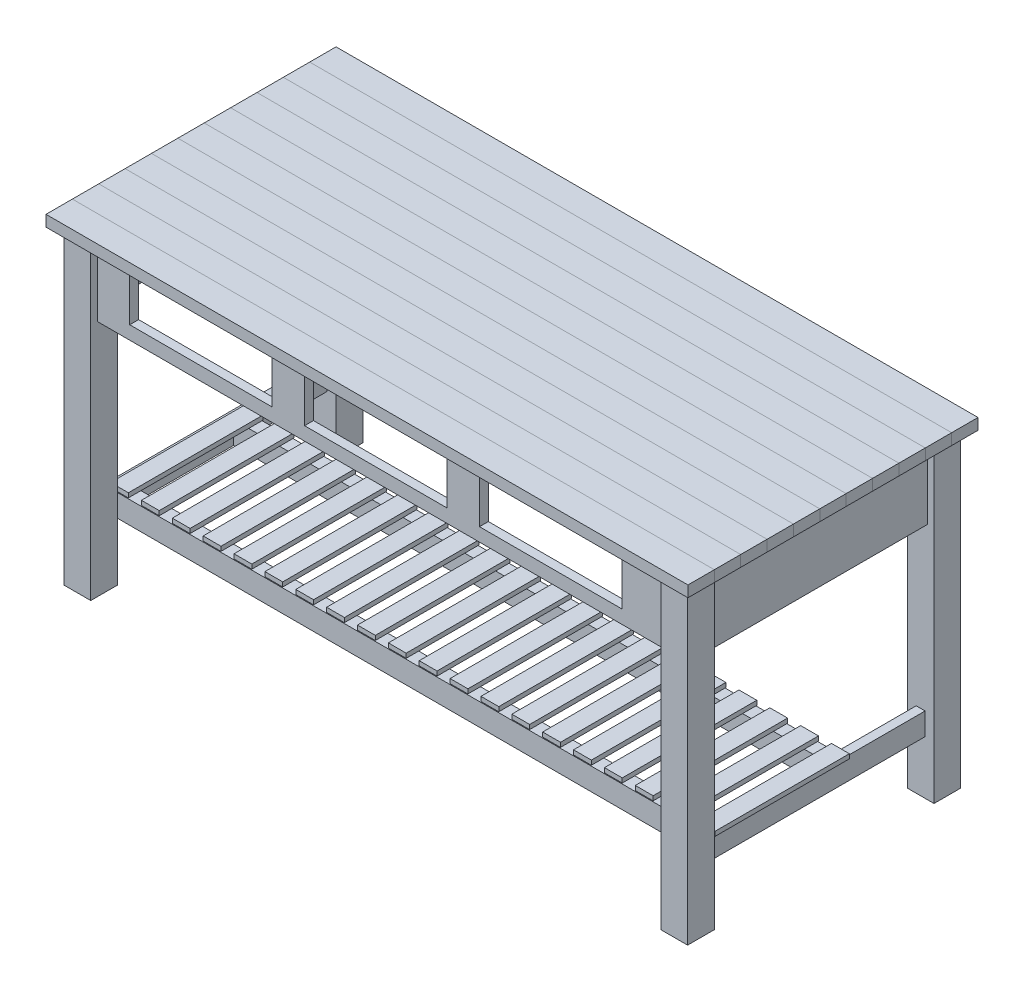
SolidWorks part; units mm, degrees
ref_plane "Default Plane" through (914.4, 31.75, 137.455) normal (0, -1, 0) x (-1, 0, 0)
sketch3d "Bounding-Box_Cut-List-Item1"
  line L0 (0, 75.184, 0) -> (1830.3875, 75.184, 0) construction
  line L1 (1830.3875, 75.184, 0) -> (1830.3875, 0, 0) construction
  line L2 (1830.3875, 0, 0) -> (0, 0, 0) construction
  line L3 (0, 0, 0) -> (0, 75.184, 0) construction
  line L4 (0, 75.184, 31.75) -> (1830.3875, 75.184, 31.75) construction
  line L5 (1830.3875, 75.184, 31.75) -> (1830.3875, 0, 31.75) construction
  line L6 (1830.3875, 0, 31.75) -> (0, 0, 31.75) construction
  line L7 (0, 0, 31.75) -> (0, 75.184, 31.75) construction
  line L8 (0, 75.184, 0) -> (0, 75.184, 31.75) construction
  line L9 (1830.3875, 75.184, 0) -> (1830.3875, 75.184, 31.75) construction
  line L10 (1830.3875, 0, 0) -> (1830.3875, 0, 31.75) construction
  line L11 (0, 0, 0) -> (0, 0, 31.75) construction
ref_plane "Default Plane" through (890.5875, 0, -664.169) normal (-1, 0, 0) x (0, 0, 1)
sketch3d "Bounding-Box_Cut-List-Item4"
  line L0 (76.2, 0, 0) -> (76.2, -882.65, 0) construction
  line L1 (76.2, -882.65, 0) -> (0, -882.65, 0) construction
  line L2 (0, -882.65, 0) -> (0, 0, 0) construction
  line L3 (0, 0, 0) -> (76.2, 0, 0) construction
  line L4 (76.2, 0, 76.2) -> (76.2, -882.65, 76.2) construction
  line L5 (76.2, -882.65, 76.2) -> (0, -882.65, 76.2) construction
  line L6 (0, -882.65, 76.2) -> (0, 0, 76.2) construction
  line L7 (0, 0, 76.2) -> (76.2, 0, 76.2) construction
  line L8 (76.2, 0, 0) -> (76.2, 0, 76.2) construction
  line L9 (76.2, -882.65, 0) -> (76.2, -882.65, 76.2) construction
  line L10 (0, -882.65, 0) -> (0, -882.65, 76.2) construction
  line L11 (0, 0, 0) -> (0, 0, 76.2) construction
ref_plane "Default Plane" through (865.1875, -666.75, -587.969) normal (-1, 0, 0) x (0, 0, 1)
sketch3d "Bounding-Box_Cut-List-Item5"
  line L0 (0, -63.5, 0) -> (624.84, -63.5, 0) construction
  line L1 (624.84, -63.5, 0) -> (624.84, 0, 0) construction
  line L2 (624.84, 0, 0) -> (0, 0, 0) construction
  line L3 (0, 0, 0) -> (0, -63.5, 0) construction
  line L4 (0, -63.5, 25.4) -> (624.84, -63.5, 25.4) construction
  line L5 (624.84, -63.5, 25.4) -> (624.84, 0, 25.4) construction
  line L6 (624.84, 0, 25.4) -> (0, 0, 25.4) construction
  line L7 (0, 0, 25.4) -> (0, -63.5, 25.4) construction
  line L8 (0, -63.5, 0) -> (0, -63.5, 25.4) construction
  line L9 (624.84, -63.5, 0) -> (624.84, -63.5, 25.4) construction
  line L10 (624.84, 0, 0) -> (624.84, 0, 25.4) construction
  line L11 (0, 0, 0) -> (0, 0, 25.4) construction
ref_plane "Default Plane" through (-812.8, 0, 36.871) normal (-1, 0, 0) x (0, 0, 1)
sketch3d "Bounding-Box_Cut-List-Item6"
  line L0 (76.2, 0, 0) -> (76.2, -882.65, 0) construction
  line L1 (76.2, -882.65, 0) -> (-701.04, -882.65, 0) construction
  line L2 (-701.04, -882.65, 0) -> (-701.04, 0, 0) construction
  line L3 (-701.04, 0, 0) -> (76.2, 0, 0) construction
  line L4 (76.2, 0, 77.7875) -> (76.2, -882.65, 77.7875) construction
  line L5 (76.2, -882.65, 77.7875) -> (-701.04, -882.65, 77.7875) construction
  line L6 (-701.04, -882.65, 77.7875) -> (-701.04, 0, 77.7875) construction
  line L7 (-701.04, 0, 77.7875) -> (76.2, 0, 77.7875) construction
  line L8 (76.2, 0, 0) -> (76.2, 0, 77.7875) construction
  line L9 (76.2, -882.65, 0) -> (76.2, -882.65, 77.7875) construction
  line L10 (-701.04, -882.65, 0) -> (-701.04, -882.65, 77.7875) construction
  line L11 (-701.04, 0, 0) -> (-701.04, 0, 77.7875) construction
material "Beech"
ref_plane "Front Plane" through (0, 0, 0) normal (0, 0, 1) x (1, 0, 0)
ref_plane "Top Plane" through (0, 0, 0) normal (0, 1, 0) x (1, 0, 0)
ref_plane "Right Plane" through (0, 0, 0) normal (1, 0, 0) x (0, 0, -1)
sketch "Sketch1" plane through (0, 0, 0) normal (0, 1, 0) x (1, 0, 0)
  line L0 (0, -450.3596) -> (0, 450.3596) construction
  line L1 (-915.9875, -62.271) -> (914.4, -62.271)
  line L2 (-915.9875, -62.271) -> (-915.9875, -137.455)
  line L3 (-915.9875, -137.455) -> (914.4, -137.455)
  line L4 (914.4, -62.271) -> (914.4, -137.455)
  line L6 (-915.9875, -62.271) -> (914.4, -62.271)
  line L7 (-915.9875, -62.271) -> (-915.9875, 12.913)
  line L8 (-915.9875, 12.913) -> (914.4, 12.913)
  line L9 (914.4, -62.271) -> (914.4, 12.913)
  line L10 (-915.9875, 12.913) -> (914.4, 12.913)
  line L11 (-915.9875, 12.913) -> (-915.9875, 88.097)
  line L12 (-915.9875, 88.097) -> (914.4, 88.097)
  line L13 (914.4, 12.913) -> (914.4, 88.097)
  line L14 (-915.9875, 88.097) -> (914.4, 88.097)
  line L15 (-915.9875, 88.097) -> (-915.9875, 163.281)
  line L16 (-915.9875, 163.281) -> (914.4, 163.281)
  line L17 (914.4, 88.097) -> (914.4, 163.281)
  line L18 (-915.9875, 163.281) -> (914.4, 163.281)
  line L19 (-915.9875, 163.281) -> (-915.9875, 238.465)
  line L20 (-915.9875, 238.465) -> (914.4, 238.465)
  line L21 (914.4, 163.281) -> (914.4, 238.465)
  line L22 (-915.9875, 238.465) -> (914.4, 238.465)
  line L23 (-915.9875, 238.465) -> (-915.9875, 313.649)
  line L24 (-915.9875, 313.649) -> (914.4, 313.649)
  line L25 (914.4, 238.465) -> (914.4, 313.649)
  line L26 (-915.9875, 313.649) -> (914.4, 313.649)
  line L27 (-915.9875, 313.649) -> (-915.9875, 388.833)
  line L28 (-915.9875, 388.833) -> (914.4, 388.833)
  line L29 (914.4, 313.649) -> (914.4, 388.833)
  line L30 (-915.9875, 388.833) -> (914.4, 388.833)
  line L31 (-915.9875, 388.833) -> (-915.9875, 464.017)
  line L32 (-915.9875, 464.017) -> (914.4, 464.017)
  line L33 (914.4, 388.833) -> (914.4, 464.017)
  line L34 (-915.9875, 464.017) -> (914.4, 464.017)
  line L35 (-915.9875, 464.017) -> (-915.9875, 539.201)
  line L36 (-915.9875, 539.201) -> (914.4, 539.201)
  line L37 (914.4, 464.017) -> (914.4, 539.201)
  line L38 (-915.9875, 539.201) -> (914.4, 539.201)
  line L39 (-915.9875, 539.201) -> (-915.9875, 614.385)
  line L40 (-915.9875, 614.385) -> (914.4, 614.385)
  line L41 (914.4, 539.201) -> (914.4, 614.385)
  line L42 (-915.9875, 614.385) -> (914.4, 614.385)
  line L44 (-915.9875, 614.385) -> (914.4, 614.385)
  line L46 (914.4, -137.455) -> (-915.9875, -137.455)
  line L47 (-915.9875, 614.385) -> (914.4, 614.385)
  line L48 (-915.9875, 614.385) -> (-915.9875, 689.569)
  line L49 (-915.9875, 689.569) -> (914.4, 689.569)
  line L50 (914.4, 614.385) -> (914.4, 689.569)
  dimension "D1" = 75.184
  dimension "D2" = 1830.3875
  dimension "D3" = 914.4
  dimension "D4" = 75.184
extrude "top1" add sketch "Sketch1" along normal blind 31.75 contours L4 L1 L2 L3 region at (-0.7938, 0, 99.863)
extrude "top2" add sketch "Sketch1<9>" along normal blind 31.75 separate body contours L1 L9 L8 L7 region at (-0.7938, 0, 24.679)
sketch "Sketch1<9>" plane through (0, 0, 0) normal (0, 1, 0) x (1, 0, 0) same geometry as "Sketch1"
extrude "top3" add sketch "Sketch1<10>" along normal blind 31.75 separate body contours L8 L13 L12 L11 region at (-0.7938, 0, -50.505)
sketch "Sketch1<10>" plane through (0, 0, 0) normal (0, 1, 0) x (1, 0, 0) same geometry as "Sketch1"
extrude "top4" add sketch "Sketch1<11>" along normal blind 31.75 separate body contours L12 L17 L16 L15 region at (-0.7938, 0, -125.689)
sketch "Sketch1<11>" plane through (0, 0, 0) normal (0, 1, 0) x (1, 0, 0) same geometry as "Sketch1"
extrude "top5" add sketch "Sketch1<12>" along normal blind 31.75 separate body contours L16 L21 L20 L19 region at (-0.7938, 0, -200.873)
sketch "Sketch1<12>" plane through (0, 0, 0) normal (0, 1, 0) x (1, 0, 0) same geometry as "Sketch1"
extrude "top6" add sketch "Sketch1<13>" along normal blind 31.75 separate body contours L20 L25 L24 L23 region at (-0.7938, 0, -276.057)
sketch "Sketch1<13>" plane through (0, 0, 0) normal (0, 1, 0) x (1, 0, 0) same geometry as "Sketch1"
extrude "top7" add sketch "Sketch1<14>" along normal blind 31.75 separate body contours L24 L29 L28 L27 region at (-0.7938, 0, -351.241)
sketch "Sketch1<14>" plane through (0, 0, 0) normal (0, 1, 0) x (1, 0, 0) same geometry as "Sketch1"
extrude "top8" add sketch "Sketch1<15>" along normal blind 31.75 separate body contours L28 L33 L32 L31 region at (-0.7938, 0, -426.425)
sketch "Sketch1<15>" plane through (0, 0, 0) normal (0, 1, 0) x (1, 0, 0) same geometry as "Sketch1"
extrude "top9" add sketch "Sketch1<16>" along normal blind 31.75 separate body contours L32 L37 L36 L35 region at (-0.7938, 0, -501.609)
sketch "Sketch1<16>" plane through (0, 0, 0) normal (0, 1, 0) x (1, 0, 0) same geometry as "Sketch1"
extrude "top10" add sketch "Sketch1<17>" along normal blind 31.75 separate body contours L36 L41 L40 L39 region at (-0.7938, 0, -576.793)
sketch "Sketch1<17>" plane through (0, 0, 0) normal (0, 1, 0) x (1, 0, 0) same geometry as "Sketch1"
extrude "top11" add sketch "Sketch1<20>" along normal blind 31.75 separate body contours L3 L49 region at (-0.7938, 0, -651.977)
sketch "Sketch1<20>" plane through (0, 0, 0) normal (0, 1, 0) x (1, 0, 0) same geometry as "Sketch1"
sketch "Sketch2" plane through (0, 0, 0) normal (0, 1, 0) x (1, 0, 0)
  line L0 (-915.9875, 614.385) -> (-915.9875, 689.569) construction
  line L1 (-889, -113.071) -> (-812.8, -113.071)
  line L2 (-889, -113.071) -> (-889, -36.871)
  line L3 (-889, -36.871) -> (-812.8, -36.871)
  line L4 (-812.8, -113.071) -> (-812.8, -36.871)
  line L5 (-890.5875, 587.969) -> (-814.3875, 587.969)
  line L6 (-890.5875, 587.969) -> (-890.5875, 664.169)
  line L7 (-890.5875, 664.169) -> (-814.3875, 664.169)
  line L8 (-814.3875, 587.969) -> (-814.3875, 664.169)
  line L10 (0, -1000) -> (0, 49000) construction
  line L11 (814.3875, 587.969) -> (814.3875, 664.169)
  line L12 (890.5875, 664.169) -> (814.3875, 664.169)
  line L13 (890.5875, 587.969) -> (890.5875, 664.169)
  line L14 (890.5875, 587.969) -> (814.3875, 587.969)
  line L15 (812.8, -113.071) -> (812.8, -36.871)
  line L16 (889, -36.871) -> (812.8, -36.871)
  line L17 (889, -113.071) -> (889, -36.871)
  line L18 (889, -113.071) -> (812.8, -113.071)
  line L20 (-915.9875, 689.569) -> (914.4, 689.569) construction
  dimension "D1" = 76.2
  dimension "D2" = 76.2
  dimension "D3" = 25.4
  dimension "D4" = 25.4
extrude "table legs" add sketch "Sketch2" against normal blind 882.65 separate body
ref_plane "Plane6" through (0, 0, -587.969) normal (0, 0, 1) x (1, 0, 0)
sketch "Sketch4" plane through (0, 0, -587.969) normal (0, 0, 1) x (1, 0, 0)
  line L0 (814.3875, -882.65) -> (890.5875, -882.65) construction
  line L1 (839.7875, -666.75) -> (865.1875, -666.75)
  line L2 (839.7875, -666.75) -> (839.7875, -730.25)
  line L3 (839.7875, -730.25) -> (865.1875, -730.25)
  line L4 (865.1875, -666.75) -> (865.1875, -730.25)
  line L5 (814.3875, -882.65) -> (814.3875, 0) construction
  line L6 (890.5875, -882.65) -> (890.5875, 0) construction
  point P4 (852.4875, -882.65)
  dimension "D1" = 152.4
  dimension "D2" = 25.4
  dimension "D3" = 63.5
  dimension "D4" = 25.4
extrude "stretcher width" add sketch "Sketch4" along normal up to surface (624.84 mm away) separate body up to face at (850.9, -441.325, 36.871)
mirror "Mirror4" about plane through (0, 0, 0) normal (1, 0, 0) of "stretcher width"
ref_plane "Plane7" through (-839.7875, 0, 0) normal (1, 0, 0) x (0, 0, -1)
sketch "Sketch5" plane through (-839.7875, 0, 0) normal (1, 0, 0) x (0, 0, -1)
  line L1 (-36.871, -666.75) -> (587.969, -666.75) construction
  line L2 (-24.171, -666.75) -> (13.929, -666.75)
  line L3 (-24.171, -666.75) -> (-24.171, -730.25)
  line L4 (-24.171, -730.25) -> (13.929, -730.25)
  line L5 (13.929, -666.75) -> (13.929, -730.25)
  line L6 (-36.871, -730.25) -> (587.969, -730.25) construction
  line L7 (-36.871, -882.65) -> (-36.871, 0) construction
  line L8 (587.969, -666.75) -> (587.969, -730.25) construction
  line L9 (359.369, -666.75) -> (321.269, -666.75)
  line L10 (359.369, -666.75) -> (359.369, -730.25)
  line L11 (359.369, -730.25) -> (321.269, -730.25)
  line L12 (321.269, -666.75) -> (321.269, -730.25)
  dimension "D1" = 12.7
  dimension "D2" = 38.1
  dimension "D3" = 228.6
  dimension "D4" = 38.1
extrude "stretcher length" add sketch "Sketch5" along normal up to surface (1679.575 mm away) separate body up to face at (839.7875, -698.5, -275.549)
ref_plane "Plane9" through (-812.8, 0, 0) normal (1, 0, 0) x (0, 0, -1)
sketch "Sketch7" plane through (-812.8, 0, 0) normal (1, 0, 0) x (0, 0, -1)
  line L0 (-113.071, 0) -> (-36.871, 0) construction
  line L1 (-94.021, 0) -> (-68.621, 0)
  line L2 (-94.021, 0) -> (-94.021, -203.2)
  line L3 (-94.021, -203.2) -> (-68.621, -203.2)
  line L4 (-68.621, 0) -> (-68.621, -203.2)
  line L5 (-113.071, -882.65) -> (-113.071, 0) construction
  dimension "D1" = 19.05
  dimension "D2" = 25.4
  dimension "D3" = 203.2
extrude "front face plate" add sketch "Sketch7" along normal up to surface (1625.6 mm away) separate body up to face at (812.8, -441.325, 74.971)
sketch "Sketch8" plane through (0, 0, -587.969) normal (0, 0, 1) x (1, 0, 0)
  line L0 (814.3875, 0) -> (890.5875, 0) construction
  line L1 (871.5375, 0) -> (846.1375, 0)
  line L2 (871.5375, 0) -> (871.5375, -203.2)
  line L3 (871.5375, -203.2) -> (846.1375, -203.2)
  line L4 (846.1375, 0) -> (846.1375, -203.2)
  line L5 (890.5875, -882.65) -> (890.5875, 0) construction
  line L6 (-890.5875, 0) -> (-814.3875, 0) construction
  line L7 (-871.5375, 0) -> (-846.1375, 0)
  line L8 (-871.5375, 0) -> (-871.5375, -203.2)
  line L9 (-871.5375, -203.2) -> (-846.1375, -203.2)
  line L10 (-846.1375, 0) -> (-846.1375, -203.2)
  line L11 (-890.5875, -882.65) -> (-890.5875, 0) construction
  dimension "D1" = 19.05
  dimension "D2" = 25.4
  dimension "D3" = 203.2
  dimension "D4" = 19.05
  dimension "D5" = 25.4
  dimension "D6" = 203.2
extrude "side face plates" add sketch "Sketch8" along normal up to surface (624.84 mm away) separate body up to face at (-850.9, -441.325, 36.871)
ref_plane "Plane10" through (0, 0, -359.369) normal (0, 0, -1) x (-1, 0, 0)
sketch "Sketch9" plane through (0, 0, -359.369) normal (0, 0, -1) x (-1, 0, 0)
  line L0 (-789.8042, -664.4034) -> (-739.0042, -664.4034)
  line L1 (-877.8152, -664.4034) -> (-827.0152, -664.4034)
  line L2 (-877.8152, -664.4034) -> (-877.8152, -651.7034)
  line L3 (-877.8152, -651.7034) -> (-827.0152, -651.7034)
  line L4 (-827.0152, -664.4034) -> (-827.0152, -651.7034)
  line L5 (-789.8042, -664.4034) -> (-789.8042, -651.7034)
  line L6 (-789.8042, -651.7034) -> (-739.0042, -651.7034)
  line L7 (-739.0042, -664.4034) -> (-739.0042, -651.7034)
  line L8 (-701.7932, -664.4034) -> (-650.9932, -664.4034)
  line L9 (-701.7932, -664.4034) -> (-701.7932, -651.7034)
  line L10 (-701.7932, -651.7034) -> (-650.9932, -651.7034)
  line L11 (-650.9932, -664.4034) -> (-650.9932, -651.7034)
  line L12 (-613.7822, -664.4034) -> (-562.9822, -664.4034)
  line L13 (-613.7822, -664.4034) -> (-613.7822, -651.7034)
  line L14 (-613.7822, -651.7034) -> (-562.9822, -651.7034)
  line L15 (-562.9822, -664.4034) -> (-562.9822, -651.7034)
  line L16 (-525.7712, -664.4034) -> (-474.9712, -664.4034)
  line L17 (-525.7712, -664.4034) -> (-525.7712, -651.7034)
  line L18 (-525.7712, -651.7034) -> (-474.9712, -651.7034)
  line L19 (-474.9712, -664.4034) -> (-474.9712, -651.7034)
  line L20 (-437.7602, -664.4034) -> (-386.9602, -664.4034)
  line L21 (-437.7602, -664.4034) -> (-437.7602, -651.7034)
  line L22 (-437.7602, -651.7034) -> (-386.9602, -651.7034)
  line L23 (-386.9602, -664.4034) -> (-386.9602, -651.7034)
  line L24 (-349.7492, -664.4034) -> (-298.9492, -664.4034)
  line L25 (-349.7492, -664.4034) -> (-349.7492, -651.7034)
  line L26 (-349.7492, -651.7034) -> (-298.9492, -651.7034)
  line L27 (-298.9492, -664.4034) -> (-298.9492, -651.7034)
  line L28 (-261.7382, -664.4034) -> (-210.9382, -664.4034)
  line L29 (-261.7382, -664.4034) -> (-261.7382, -651.7034)
  line L30 (-261.7382, -651.7034) -> (-210.9382, -651.7034)
  line L31 (-210.9382, -664.4034) -> (-210.9382, -651.7034)
  line L32 (-173.7272, -664.4034) -> (-122.9272, -664.4034)
  line L33 (-173.7272, -664.4034) -> (-173.7272, -651.7034)
  line L34 (-173.7272, -651.7034) -> (-122.9272, -651.7034)
  line L35 (-122.9272, -664.4034) -> (-122.9272, -651.7034)
  line L36 (-85.7162, -664.4034) -> (-34.9162, -664.4034)
  line L37 (-85.7162, -664.4034) -> (-85.7162, -651.7034)
  line L38 (-85.7162, -651.7034) -> (-34.9162, -651.7034)
  line L39 (-34.9162, -664.4034) -> (-34.9162, -651.7034)
  line L40 (2.2948, -664.4034) -> (53.0948, -664.4034)
  line L41 (2.2948, -664.4034) -> (2.2948, -651.7034)
  line L42 (2.2948, -651.7034) -> (53.0948, -651.7034)
  line L43 (53.0948, -664.4034) -> (53.0948, -651.7034)
  line L44 (90.3058, -664.4034) -> (141.1058, -664.4034)
  line L45 (90.3058, -664.4034) -> (90.3058, -651.7034)
  line L46 (90.3058, -651.7034) -> (141.1058, -651.7034)
  line L47 (141.1058, -664.4034) -> (141.1058, -651.7034)
  line L48 (178.3168, -664.4034) -> (229.1168, -664.4034)
  line L49 (178.3168, -664.4034) -> (178.3168, -651.7034)
  line L50 (178.3168, -651.7034) -> (229.1168, -651.7034)
  line L51 (229.1168, -664.4034) -> (229.1168, -651.7034)
  line L52 (266.3278, -664.4034) -> (317.1278, -664.4034)
  line L53 (266.3278, -664.4034) -> (266.3278, -651.7034)
  line L54 (266.3278, -651.7034) -> (317.1278, -651.7034)
  line L55 (317.1278, -664.4034) -> (317.1278, -651.7034)
  line L56 (354.3388, -664.4034) -> (405.1388, -664.4034)
  line L57 (354.3388, -664.4034) -> (354.3388, -651.7034)
  line L58 (354.3388, -651.7034) -> (405.1388, -651.7034)
  line L59 (405.1388, -664.4034) -> (405.1388, -651.7034)
  line L60 (442.3498, -664.4034) -> (493.1498, -664.4034)
  line L61 (442.3498, -664.4034) -> (442.3498, -651.7034)
  line L62 (442.3498, -651.7034) -> (493.1498, -651.7034)
  line L63 (493.1498, -664.4034) -> (493.1498, -651.7034)
  line L64 (530.3608, -664.4034) -> (581.1608, -664.4034)
  line L65 (530.3608, -664.4034) -> (530.3608, -651.7034)
  line L66 (530.3608, -651.7034) -> (581.1608, -651.7034)
  line L67 (581.1608, -664.4034) -> (581.1608, -651.7034)
  line L68 (618.3718, -664.4034) -> (669.1718, -664.4034)
  line L69 (618.3718, -664.4034) -> (618.3718, -651.7034)
  line L70 (618.3718, -651.7034) -> (669.1718, -651.7034)
  line L71 (669.1718, -664.4034) -> (669.1718, -651.7034)
  line L72 (706.3828, -664.4034) -> (757.1828, -664.4034)
  line L73 (706.3828, -664.4034) -> (706.3828, -651.7034)
  line L74 (706.3828, -651.7034) -> (757.1828, -651.7034)
  line L75 (757.1828, -664.4034) -> (757.1828, -651.7034)
  line L76 (794.3938, -664.4034) -> (845.1938, -664.4034)
  line L77 (794.3938, -664.4034) -> (794.3938, -651.7034)
  line L78 (794.3938, -651.7034) -> (845.1938, -651.7034)
  line L79 (845.1938, -664.4034) -> (845.1938, -651.7034)
  dimension "D1" = 38.1
  dimension "D2" = 50.8
  dimension "D3" = 12.7
  dimension "D4" = 20
extrude "stretcher rack boards" add sketch "Sketch9" against normal up to surface (383.54 mm away) separate body up to face at (0, -698.5, 24.171)
ref_plane "Plane11" through (0, 0, 94.021) normal (0, 0, 1) x (1, 0, 0)
sketch "Sketch10" plane through (0, 0, 94.021) normal (0, 0, 1) x (1, 0, 0)
  line L0 (-812.8, 0) -> (-812.8, -203.2) construction
  line L1 (-720.725, -38.1) -> (-314.325, -38.1)
  line L2 (-720.725, -38.1) -> (-720.725, -165.1)
  line L3 (-720.725, -165.1) -> (-314.325, -165.1)
  line L4 (-314.325, -38.1) -> (-314.325, -165.1)
  line L5 (812.8, 0) -> (-812.8, 0) construction
  line L6 (812.8, -203.2) -> (-812.8, -203.2) construction
  line L7 (-222.123, -38.1) -> (184.277, -38.1)
  line L8 (-222.123, -38.1) -> (-222.123, -165.1)
  line L9 (-222.123, -165.1) -> (184.277, -165.1)
  line L10 (184.277, -38.1) -> (184.277, -165.1)
  line L11 (276.479, -38.1) -> (682.879, -38.1)
  line L12 (276.479, -38.1) -> (276.479, -165.1)
  line L13 (276.479, -165.1) -> (682.879, -165.1)
  line L14 (682.879, -38.1) -> (682.879, -165.1)
  dimension "D1" = 92.075
  dimension "D2" = 38.1
  dimension "D3" = 38.1
  dimension "D4" = 406.4
  dimension "D5" = 3
extrude "drawer cut outs" cut sketch "Sketch10" against normal up to next (25.4 mm away)
ref_plane "Plane12" through (-814.3875, 0, 0) normal (1, 0, 0) x (0, 0, -1)
sketch "Sketch11" plane through (-814.3875, 0, 0) normal (1, 0, 0) x (0, 0, -1)
  line L0 (587.969, 0) -> (664.169, 0) construction
  line L1 (645.119, 0) -> (619.719, 0)
  line L2 (645.119, 0) -> (645.119, -101.6)
  line L3 (645.119, -101.6) -> (619.719, -101.6)
  line L4 (619.719, 0) -> (619.719, -101.6)
  line L5 (664.169, -882.65) -> (664.169, 0) construction
  dimension "D1" = 19.05
  dimension "D2" = 101.6
  dimension "D3" = 25.4
extrude "back face plate" add sketch "Sketch11" along normal up to surface (1628.775 mm away) separate body up to face at (814.3875, -441.325, -626.069)
equation "\"table_thickness\" = 1.0625"
equation "\"D1@top1\"=\"table_thickness\""
equation "\"D1@top2\"=\"table_thickness\""
equation "\"D1@top3\"=\"table_thickness\""
equation "\"D1@top4\"=\"table_thickness\""
equation "\"D1@top5\"=\"table_thickness\""
equation "\"D1@top6\"=\"table_thickness\""
equation "\"D1@top7\"=\"table_thickness\""
equation "\"D1@top8\"=\"table_thickness\""
equation "\"D1@top9\"=\"table_thickness\""
equation "\"D1@top10\"=\"table_thickness\""
equation "\"D1@top11\"= \"table_thickness\""
